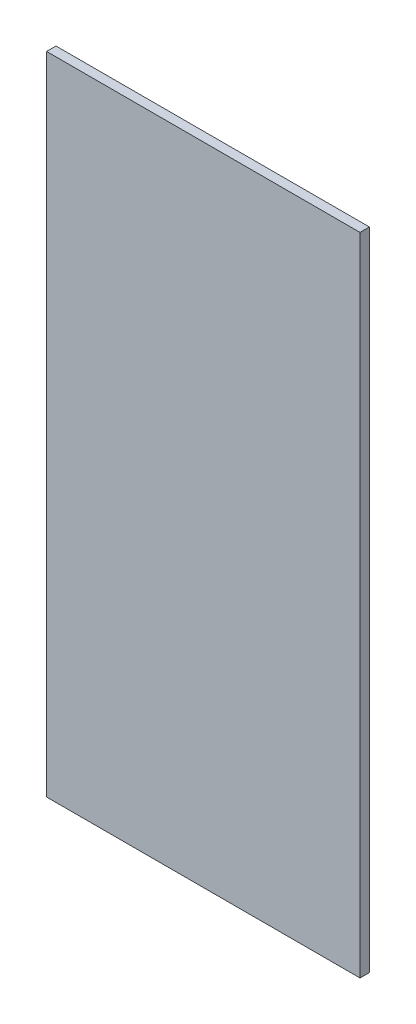
SolidWorks part; units mm, degrees
material "PET"
ref_plane "Front Plane" through (0, 0, 0) normal (0, 0, 1) x (1, 0, 0)
ref_plane "Top Plane" through (0, 0, 0) normal (0, 1, 0) x (1, 0, 0)
ref_plane "Right Plane" through (0, 0, 0) normal (1, 0, 0) x (0, 0, -1)
sketch "Sketch1" plane through (0, 0, 0) normal (0, 0, 1) x (1, 0, 0)
  line L1 (-28.5714, 389.1048) -> (171.4286, 389.1048)
  line L2 (-28.5714, 389.1048) -> (-28.5714, -22.8952)
  line L3 (-28.5714, -22.8952) -> (171.4286, -22.8952)
  line L4 (171.4286, 389.1048) -> (171.4286, -22.8952)
  dimension "D1" = 412
  dimension "D2" = 200
extrude "Boss-Extrude1" add sketch "Sketch1" along normal blind 6
